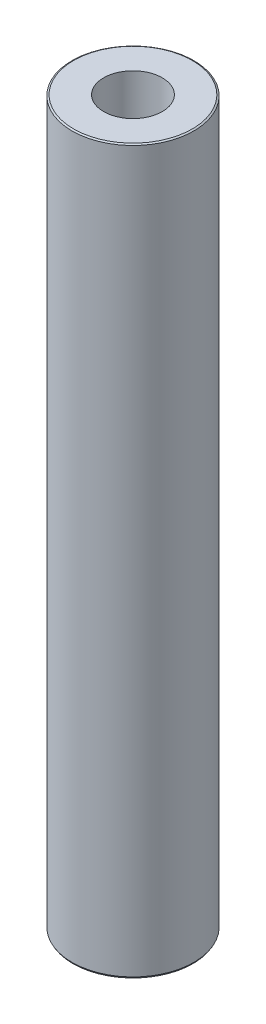
SolidWorks part; units mm, degrees
ref_plane "Front Plane" through (0, 0, 0) normal (0, 0, 1) x (1, 0, 0)
ref_plane "Top Plane" through (0, 0, 0) normal (0, 1, 0) x (1, 0, 0)
ref_plane "Right Plane" through (0, 0, 0) normal (1, 0, 0) x (0, 0, -1)
sketch "Sketch1" plane through (0, 0, 0) normal (0, 1, 0) x (1, 0, 0)
  circle A0 centre (0, 0) radius 20
  dimension "SHAFT_OD" = 40
extrude "Boss-Extrude1" add sketch "Sketch1" along normal blind 237.1318
sketch "Sketch2" plane through (0, 0, 0) normal (0, 1, 0) x (1, 0, 0)
  circle A0 centre (0, 0) radius 9.6206
  dimension "BORE_D" = 19.2413
extrude "Cut-Extrude1" cut sketch "Sketch2" along normal through all
chamfer "Chamfer1" distance 0.301 angle 60 2 edges at (0, 237.1318, 20) (0, 0, 20) first distance on face at (0, 237.1318, 20) first distance on face at (0, 0, 9.6206)
